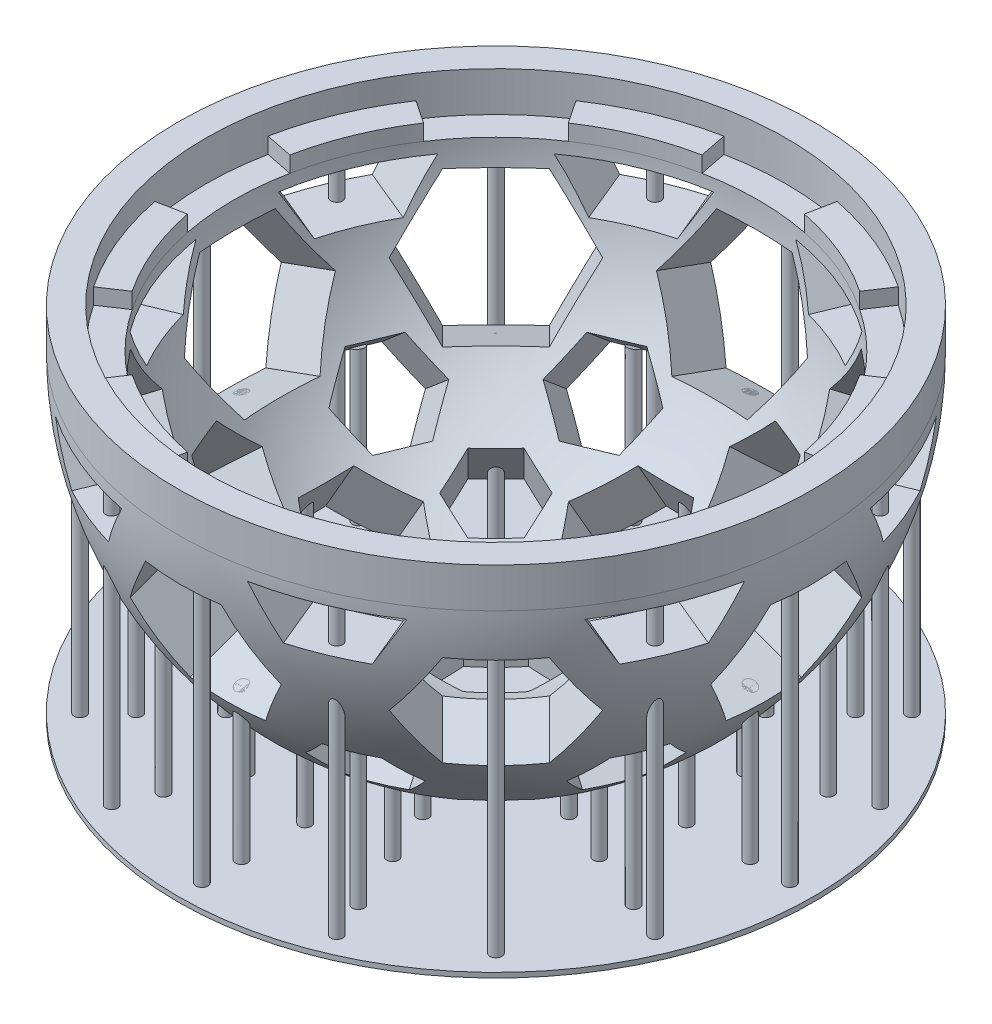
SolidWorks part; units mm, degrees
ref_plane "Front Plane" through (0, 0, 0) normal (0, 0, 1) x (1, 0, 0)
ref_plane "Top Plane" through (0, 0, 0) normal (0, 1, 0) x (1, 0, 0)
ref_plane "Right Plane" through (0, 0, 0) normal (1, 0, 0) x (0, 0, -1)
sketch "Sketch1" plane through (0, 0, 0) normal (0, 0, 1) x (1, 0, 0)
  line L0 (0, -40) -> (0, -33)
  line L2 (-40, 0) -> (-33, 0)
  arc A0 (-40, 0) -> (0, -40) centre (0, 0) ccw
  arc A1 (-33, 0) -> (0, -33) centre (0, 0) ccw
  dimension "D1" = 80
  dimension "D2" = 66
revolve "Revolve1" add sketch "Sketch1" angle 360 about L0
sketch "Sketch2" plane through (0, 0, 0) normal (0, 1, 0) x (1, 0, 0)
  line L0 (-40, 0) -> (40, 0) construction
sketch "Sketch3" plane through (0, 0, 0) normal (0, 1, 0) x (1, 0, 0)
  line L0 (0, -40) -> (0, 40) construction
sketch "Sketch4" plane through (0, 0, 0) normal (0, 0, 1) x (1, 0, 0)
  line L0 (0, -40) -> (0, 40) construction
sketch "Sketch5" plane through (0, 0, 0) normal (0, 1, 0) x (1, 0, 0)
  point P0 (0, 0)
ref_plane "Plane CUT 1" through (0, 0, 0) normal (0, -0.342, 0.9397) x (1, 0, 0)
sketch "Sketch6" plane through (0, 0, 0) normal (0, -0.342, 0.9397) x (1, 0, 0)
  line L7 (4.75, -8.2272) -> (9.5, 0)
  line L8 (9.5, 0) -> (4.75, 8.2272)
  line L9 (4.75, 8.2272) -> (-4.75, 8.2272)
  line L10 (-4.75, 8.2272) -> (-9.5, 0)
  line L11 (-9.5, 0) -> (-4.75, -8.2272)
  line L12 (-4.75, -8.2272) -> (4.75, -8.2272)
  circle A0 centre (0, 0) radius 8.2272 construction
extrude "Cut-Extrude1" cut sketch "Sketch6" along normal blind 60
pattern_circular "CirPattern1" count 8 over 360 about axis through (0, -40, 0) along (0, 1, 0) of "Cut-Extrude1" reverse direction yes
ref_plane "Plane2" through (0, 0, 0) normal (0.9239, 0, -0.3827) x (0, 1, 0)
sketch "Sketch7" plane through (0, 0, 0) normal (0.9239, 0, -0.3827) x (0, 1, 0)
  line L0 (0, -51.8688) -> (0, 51.8688) construction
ref_plane "Plane CUT 2" through (0, 0, 0) normal (0.7077, 0.6428, -0.2932) x (0.3827, 0, 0.9239)
sketch "Sketch8" plane through (0, 0, 0) normal (0.7077, 0.6428, -0.2932) x (0.3827, 0, 0.9239)
  line L1 (-2.8868, -5) -> (2.8868, -5)
  line L2 (2.8868, -5) -> (5.7735, 0)
  line L3 (5.7735, 0) -> (2.8868, 5)
  line L4 (2.8868, 5) -> (-2.8868, 5)
  line L5 (-2.8868, 5) -> (-5.7735, 0)
  line L6 (-5.7735, 0) -> (-2.8868, -5)
  circle A0 centre (0, 0) radius 5 construction
extrude "Cut-Extrude2" cut sketch "Sketch8" against normal blind 60
pattern_circular "CirPattern2" count 8 over 360 about axis through (0, -40, 0) along (0, 1, 0) of "Cut-Extrude2" reverse direction yes
ref_plane "PLANE CUT 4" through (0, 0, 0) normal (0, -0.866, 0.5) x (1, 0, 0)
sketch "Sketch9" plane through (0, 0, 0) normal (0, -0.866, 0.5) x (1, 0, 0)
  line L1 (3.5, -6.0622) -> (7, 0)
  line L2 (7, 0) -> (3.5, 6.0622)
  line L3 (3.5, 6.0622) -> (-3.5, 6.0622)
  line L4 (-3.5, 6.0622) -> (-7, 0)
  line L5 (-7, 0) -> (-3.5, -6.0622)
  line L6 (-3.5, -6.0622) -> (3.5, -6.0622)
  circle A0 centre (0, 0) radius 6.0622 construction
extrude "Cut-Extrude3" cut sketch "Sketch9" along normal blind 72
pattern_circular "CirPattern3" count 8 over 360 about axis through (0, -40, 0) along (0, 1, 0) skipping 1, 3, 5, 7 of "Cut-Extrude3" reverse direction yes
sketch "Sketch10" plane through (0, 0, 0) normal (0, 1, 0) x (1, 0, 0)
  line L0 (2.8995, -7) -> (7, -2.8995)
  line L1 (7, 2.8995) -> (2.8995, 7)
  line L2 (2.8995, 7) -> (-2.8995, 7)
  line L3 (-2.8995, 7) -> (-7, 2.8995)
  line L4 (-7, 2.8995) -> (-7, -2.8995)
  line L5 (-7, -2.8995) -> (-2.8995, -7)
  line L6 (-2.8995, -7) -> (2.8995, -7)
  line L7 (7, -2.8995) -> (7, 2.8995)
  circle A0 centre (0, 0) radius 7 construction
extrude "Cut-Extrude4" cut sketch "Sketch10" against normal blind 72
ref_plane "Plane5" through (0, 0, 0) normal (0.7071, 0, 0.7071) x (0, 1, 0)
sketch "Sketch11" plane through (0, 0, 0) normal (0.7071, 0, 0.7071) x (0, 1, 0)
  line L0 (0, -40) -> (0, 40) construction
ref_plane "PLANE CUT 3" through (0, 0, 0) normal (0.3747, 0.848, 0.3747) x (-0.7071, 0, 0.7071)
sketch "Sketch12" plane through (0, 0, 0) normal (0.3747, 0.848, 0.3747) x (-0.7071, 0, 0.7071)
  line L1 (-5, 0) -> (-2.5, -4.3301)
  line L2 (-2.5, -4.3301) -> (2.5, -4.3301)
  line L3 (2.5, -4.3301) -> (5, 0)
  line L4 (5, 0) -> (2.5, 4.3301)
  line L5 (2.5, 4.3301) -> (-2.5, 4.3301)
  line L6 (-2.5, 4.3301) -> (-5, 0)
  circle A0 centre (0, 0) radius 4.3301 construction
extrude "Cut-Extrude5" cut sketch "Sketch12" against normal blind 72
pattern_circular "CirPattern4" count 4 over 360 about axis through (0, -40, 0) along (0, 1, 0) of "Cut-Extrude5" reverse direction yes
ref_plane "Plane6" through (0, 0, 0) normal (0.3827, 0, 0.9239) x (0, 1, 0)
sketch "Sketch13" plane through (0, 0, 0) normal (0.3827, 0, 0.9239) x (0, 1, 0)
  line L0 (-1.5, 7.6797) -> (-1.5, -7.6797)
  line L2 (-1.5, 7.6797) -> (-7.4008, 4.2729)
  line L3 (-7.4008, 4.2729) -> (-7.4008, -4.2729)
  line L4 (-7.4008, -4.2729) -> (-1.5, -7.6797)
  line L7 (0, 36.9552) -> (0, -36.9552) construction
  line L8 (7.4008, 4.2729) -> (3.7004, 6.4093) [skipped]
  line L9 (7.4008, -4.2729) -> (7.4008, 0) [skipped]
  line L10 (0, -8.5457) -> (3.7004, -6.4093) [skipped]
  arc A0 (-1.5, 7.2472) -> (-1.5, -7.2472) centre (0, 0) ccw construction
  dimension "D1" = 1.5
extrude "Cut-Extrude6" cut sketch "Sketch13" against normal up to vertex (51.8688 mm away) up to point (-19.8493, 0, -47.9205)
pattern_circular "CirPattern5" count 8 over 360 about axis through (0, -40, 0) along (0, 1, 0) of "Cut-Extrude6" reverse direction yes
ref_plane "Plane7" through (0, -40, 0) normal (0, 1, 0) x (1, 0, 0)
sketch "Sketch14" plane through (0, -40, 0) normal (0, 1, 0) x (1, 0, 0)
  circle A0 centre (0, 0) radius 40
extrude "Boss-Extrude1" add sketch "Sketch14" along normal blind 0.6173 separate body
sketch "Sketch15" plane through (0, -39.3827, 0) normal (0, 1, 0) x (1, 0, 0)
  circle A0 centre (37, 0) radius 0.75
  circle A1 centre (0, 0) radius 40 construction
  dimension "D1" = 0
  dimension "D3" = 1.5
  dimension "D2" = 37
extrude "Boss-Extrude8" add sketch "Sketch15" along normal blind 38.8
pattern_circular "CirPattern6" count 16 over 360 about axis through (0, -40, 0) along (0, 1, 0) of "Boss-Extrude8" reverse direction yes
sketch "Sketch16" plane through (0, -39.3827, 0) normal (0, 1, 0) x (1, 0, 0)
  circle A0 centre (-32, 0) radius 0.75
  dimension "D1" = 1.5
  dimension "D2" = 0
  dimension "D3" = 32
extrude "Boss-Extrude13" add sketch "Sketch16" along normal blind 23
pattern_circular "CirPattern10" count 16 over 360 about axis through (0, -40, 0) along (0, 1, 0) of "Boss-Extrude13" reverse direction yes
sketch "Sketch17" plane through (0, -39.3827, 0) normal (0, 1, 0) x (1, 0, 0)
  circle A0 centre (0, 24) radius 0.75
  dimension "D1" = 1.5
  dimension "D2" = 0
  dimension "D3" = 24
extrude "Boss-Extrude16" add sketch "Sketch17" along normal blind 12
pattern_circular "CirPattern11" count 16 over 360 about axis through (0, -40, 0) along (0, 1, 0) of "Boss-Extrude16" reverse direction yes
sketch "Sketch18" plane through (0, -39.3827, 0) normal (0, 1, 0) x (1, 0, 0)
  circle A0 centre (13, 0) radius 0.75
  dimension "D1" = 1.5
  dimension "D2" = 0
  dimension "D3" = 13
extrude "Boss-Extrude17" add sketch "Sketch18" along normal blind 2.5
pattern_circular "CirPattern12" count 16 over 360 about axis through (0, -40, 0) along (0, 1, 0) of "Boss-Extrude17" reverse direction yes
sketch "Sketch19" plane through (0, -39.3827, 0) normal (0, 1, 0) x (1, 0, 0)
  line L1 (0, 0) -> (15.706, -6.5056) construction
  line L2 (-40, 0) -> (40, 0) construction
  circle A1 centre (0, 0) radius 17 construction
  circle A2 centre (15.706, -6.5056) radius 0.75
  dimension "D1" = 34
  dimension "D2" = 22.5
  dimension "D3" = 1.5
extrude "Boss-Extrude19" add sketch "Sketch19" along normal blind 5
pattern_circular "CirPattern13" count 8 over 360 about axis through (0, -40, 0) along (0, 1, 0) of "Boss-Extrude19" reverse direction yes
sketch "Sketch20" plane through (-1.9897, -7.7311, -1.9897) normal (0.2418, 0.9397, 0.2418) x (0.9703, -0.2342, -0.0603)
  circle A0 centre (24.9892, -27.1181) radius 2
  dimension "D1" = 4
extrude "Cut-Extrude7" cut sketch "Sketch20" along normal blind 5
pattern_circular "CirPattern14" count 16 over 360 about axis through (0, -40, 0) along (0, 1, 0) of "Cut-Extrude7" reverse direction yes
sketch "Sketch22" plane through (0, -1.5, 0) normal (0, -1, 0) x (1, 0, 0)
  line L0 (0, 0) -> (-9.5763, 35.7393) construction
  line L1 (0, 40) -> (0, -40) construction
  circle A0 centre (0, 0) radius 37 construction
  circle A1 centre (-9.5763, 35.7393) radius 0.75
  dimension "D1" = 74
  dimension "D3" = 1.5
  dimension "D2" = 15
ref_plane "Plane9" through (0, -7.4008, 0) normal (0, 1, 0) x (1, 0, 0)
sketch "Sketch24" plane through (0, -7.4008, 0) normal (0, 1, 0) x (1, 0, 0)
  line L0 (-11.3564, -34.9513) -> (-11.5881, -35.6646) construction
  line L1 (0, -40) -> (0, 40) construction
  arc A0 (-12.2991, -35.4257) -> (-10.8726, -35.8892) centre (0, 0) ccw construction
  circle A1 centre (-11.5881, -35.6646) radius 0.75
  dimension "D2" = 1.5
  dimension "D3" = 75
  dimension "D1" = 18
extrude "Boss-Extrude39" [suppressed] add sketch "Sketch24" along normal up to next and the other way blind 0.5
pattern_circular "CirPattern15" [suppressed] count 40 over 360 about axis through (0, -40, 0) along (0, 1, 0) reverse direction yes of bodies 127
sketch "Sketch30" plane through (-2.8139, -7.7311, 0) normal (0.342, 0.9397, 0) x (0.9397, -0.342, 0)
  circle A0 centre (35.6558, -2.7696) radius 0.9041
extrude "Boss-Extrude40" [suppressed] add sketch "Sketch30" along normal up to next
pattern_circular "CirPattern16" [suppressed] count 40 over 360 about axis through (0, -40, 0) along (0, 1, 0) reverse direction yes of bodies 129
sketch "Sketch31" plane through (0, 0, 0) normal (0, 1, 0) x (1, 0, 0)
  circle A0 centre (0, 0) radius 40
  circle A1 centre (0, 0) radius 33
  dimension "D1" = 66
extrude "Boss-Extrude41" add sketch "Sketch31" along normal blind 5
sketch "Sketch32" plane through (0, 5, 0) normal (0, 1, 0) x (1, 0, 0)
  circle A2 centre (0, 0) radius 36.5
  dimension "D1" = 73
extrude "Cut-Extrude8" cut sketch "Sketch32" against normal blind 3
sketch "Sketch37" plane through (0, 2, 0) normal (0, 1, 0) x (1, 0, 0)
  line L0 (-6.438, 32.3659) -> (-7.1208, 35.7987)
  line L1 (6.438, 32.3659) -> (7.1208, 35.7987)
  line L2 (0, -40) -> (0, 40) construction
  arc A0 (7.1208, 35.7987) -> (-7.1208, 35.7987) centre (0, 0) ccw
  arc A1 (6.438, 32.3659) -> (-6.438, 32.3659) centre (0, 0) ccw
  dimension "D3" = 36.5
  dimension "D4" = 33
  dimension "D1" = 11.25
  dimension "D2" = 11.25
extrude "Cut-Extrude11" cut sketch "Sketch37" against normal blind 2
pattern_circular "CirPattern21" count 8 over 360 about axis through (0, -40, 0) along (0, 1, 0) of "Cut-Extrude11" reverse direction yes
